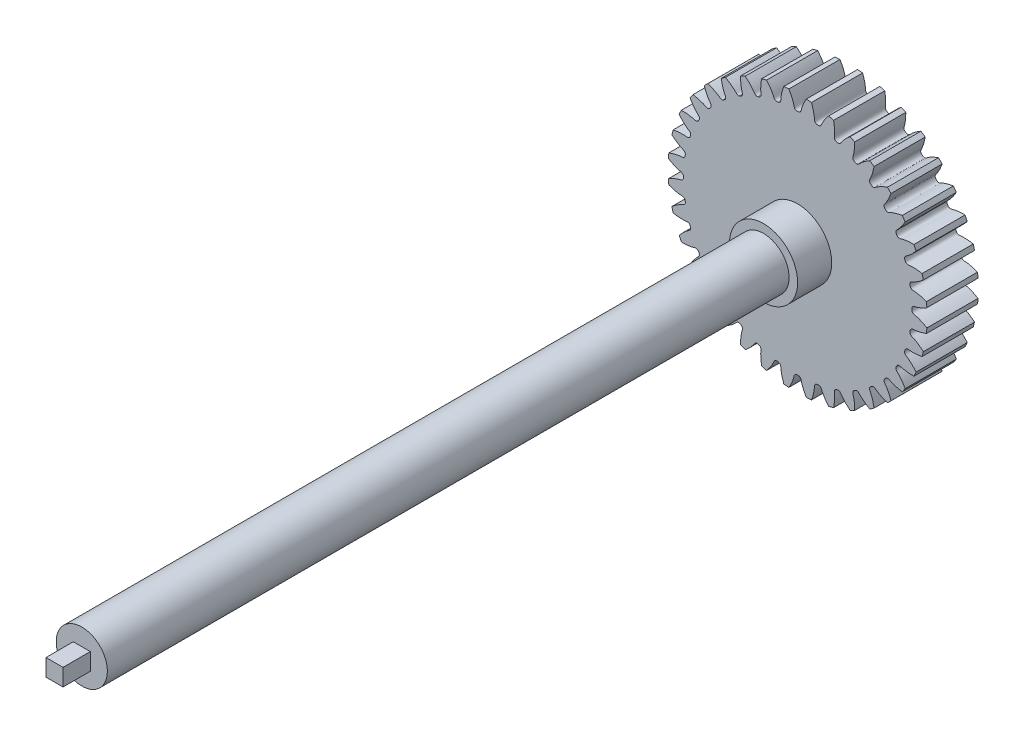
SolidWorks part; units mm, degrees
ref_plane "Front Plane" through (0, 0, 0) normal (0, 0, 1) x (1, 0, 0)
ref_plane "Top Plane" through (0, 0, 0) normal (0, 1, 0) x (1, 0, 0)
ref_plane "Right Plane" through (0, 0, 0) normal (1, 0, 0) x (0, 0, -1)
ref_axis "Axis1" through (0, 0, 55) along (0, 0, -1)
sketch "旋转草图大直齿轮" plane through (0, 0, 0) normal (1, 0, 0) x (0, 0, -1)
  line L0 (0, 0) -> (1, 0) construction
  line L1 (-7.5, 0) -> (-7.5, 38)
  line L2 (-7.5, 38) -> (7.5, 38)
  line L3 (7.5, 38) -> (7.5, 0)
  line L4 (7.5, 0) -> (-7.5, 0)
  dimension "Side1" = 7.5
  dimension "OutsideRadius" = 38
  dimension "Side2" = 7.5
revolve "大直齿轮" add sketch "旋转草图大直齿轮" angle 360 about L0
sketch "齿草图大直齿轮" plane through (0, 0, 0) normal (0, 0, 1) x (1, 0, 0)
  arc A0 (38.0098, 2.6196) -> (38.0098, -2.6196) centre (0, 0) cw
  spline S0 degree 3 poles (38.0098, -2.6196) (37.8138, -2.5003) (37.5223, -2.3306) (37.1351, -2.1211) (36.8604, -1.9796) (36.5956, -1.8501) (36.3411, -1.7319) (36.0971, -1.6246) (35.8641, -1.5278) (35.6423, -1.4409) (35.432, -1.3635) (35.2336, -1.295) (35.0473, -1.2349) (34.8734, -1.1827) (34.712, -1.138) (34.4981, -1.0822) (34.3156, -1.0475) (34.168, -1.0021) (34.1113, -0.9824) (34.0555, -0.9606) (34.0004, -0.9362) (33.9457, -0.9088) (33.891, -0.8777) (33.8362, -0.8418) (33.781, -0.7999) (33.7254, -0.7504) (33.6703, -0.6912) (33.617, -0.6201) (33.5685, -0.5354) (33.5291, -0.4365) (33.5051, -0.3307) (33.4954, -0.1836) (33.5031, 0) (33.4954, 0.1836) (33.5051, 0.3307) (33.5291, 0.4365) (33.5685, 0.5354) (33.617, 0.6201) (33.6703, 0.6912) (33.7254, 0.7504) (33.781, 0.7999) (33.8362, 0.8418) (33.891, 0.8777) (33.9457, 0.9088) (34.0004, 0.9362) (34.0555, 0.9606) (34.1113, 0.9824) (34.168, 1.0021) (34.3156, 1.0475) (34.4981, 1.0822) (34.712, 1.138) (34.8734, 1.1827) (35.0473, 1.2349) (35.2336, 1.295) (35.432, 1.3635) (35.6423, 1.4409) (35.8641, 1.5278) (36.0971, 1.6246) (36.3411, 1.7319) (36.5956, 1.8501) (36.8604, 1.9796) (37.1351, 2.1211) (37.5223, 2.3306) (37.8138, 2.5003) (38.0098, 2.6196) knots 0 0 0 0 0.062457 0.091761 0.119781 0.146518 0.171972 0.196143 0.21903 0.240634 0.260955 0.279993 0.297747 0.314218 0.329406 0.34331 0.374369 0.379859 0.385295 0.390713 0.396158 0.401682 0.407356 0.413263 0.419504 0.4262 0.433484 0.44149 0.450315 0.459977 0.470356 0.47968 0.5 0.52032 0.529644 0.540023 0.549685 0.55851 0.566516 0.5738 0.580496 0.586737 0.592644 0.598318 0.603842 0.609287 0.614705 0.620141 0.625631 0.65669 0.670594 0.685782 0.702253 0.720007 0.739045 0.759366 0.78097 0.803857 0.828028 0.853482 0.880219 0.908239 0.937543 1 1 1 1
extrude "齿拉伸切除大直齿轮" cut sketch "齿草图大直齿轮" against normal blind 7.5 and the other way blind 7.5
pattern_circular "齿形大直齿轮" count 36 every 10 about axis through (0, 0, 55) along (0, 0, -1) of "齿拉伸切除大直齿轮"
sketch "辅助草图大直齿轮" plane through (0, 0, 0) normal (0, 0, 1) x (1, 0, 0)
  circle A0 centre (0, 0) radius 36 construction
  circle A1 centre (0, 0) radius 33.8289 construction
  circle A2 centre (0, 0) radius 34.3848 construction
  circle A3 centre (0, 0) radius 38 construction
  circle A4 centre (0, 0) radius 33.5 construction
  dimension "PitchDiameter" = 72
  dimension "BaseDiameter" = 67.6579
  dimension "FormDiameter" = 68.7695
  dimension "MajorDiameter" = 76
  dimension "MinorDiameter" = 67
sketch "Sketch5" plane through (0, 0, 7.5) normal (0, 0, 1) x (1, 0, 0)
  circle A0 centre (0, 0) radius 10
  dimension "D1" = 20
extrude "Extrude2" add sketch "Sketch5" along normal blind 10
sketch "Sketch6" plane through (0, 0, 17.5) normal (0, 0, 1) x (1, 0, 0)
  circle A0 centre (0, 0) radius 7.5
  dimension "D1" = 15
extrude "Extrude3" add sketch "Sketch6" along normal blind 200
sketch "Sketch7" plane through (0, 0, 217.5) normal (0, 0, 1) x (1, 0, 0)
  line L1 (-2.5, 2.5) -> (2.5, 2.5)
  line L2 (-2.5, 2.5) -> (-2.5, -2.5)
  line L3 (-2.5, -2.5) -> (2.5, -2.5)
  line L4 (2.5, 2.5) -> (2.5, -2.5)
  line L5 (-2.5, 2.5) -> (2.5, -2.5) construction
  line L6 (-2.5, -2.5) -> (2.5, 2.5) construction
  point P0 (0, 0)
  dimension "D1" = 5
  dimension "D2" = 5
extrude "Extrude4" add sketch "Sketch7" along normal blind 8
sketch "Sketch8" plane through (0, 0, 217.5) normal (0, 0, 1) x (1, 0, 0)
  line L0 (0, 0) -> (0, 7.5)
  circle A0 centre (0, 0) radius 7.5 construction
